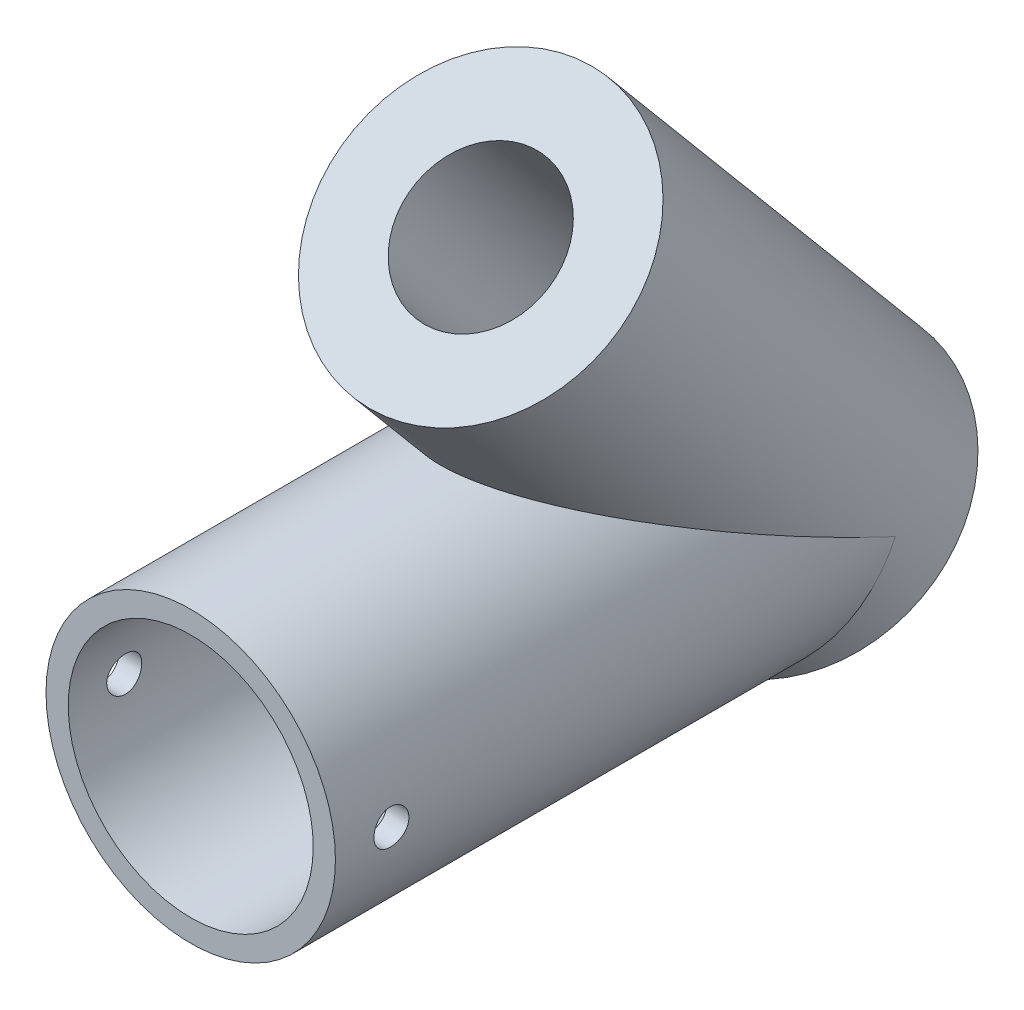
SolidWorks part; units mm, degrees
ref_plane "Front Plane" through (0, 0, 0) normal (0, 0, 1) x (1, 0, 0)
ref_plane "Top Plane" through (0, 0, 0) normal (0, 1, 0) x (1, 0, 0)
ref_plane "Right Plane" through (0, 0, 0) normal (1, 0, 0) x (0, 0, -1)
sketch "Sketch1" plane through (0, 0, 0) normal (0, 0, 1) x (1, 0, 0)
  circle A0 centre (0, 0) radius 17.5
  circle A1 centre (0, 0) radius 20.675
  dimension "D1" = 35
  dimension "D2" = 41.35
extrude "Boss-Extrude1" add sketch "Sketch1" along normal blind 60
sketch "Sketch2" plane through (0, 0, 0) normal (1, 0, 0) x (0, 0, -1)
  line L0 (0, 0) -> (20, 0) construction
  line L1 (20, 0) -> (-18.5673, 45.9627)
  dimension "D1" = 20
  dimension "D2" = 50
  dimension "D3" = 60
ref_plane "Plane4" through (0, 45.9627, 18.5673) normal (0, 0.766, 0.6428) x (1, 0, 0)
sketch "Sketch3" plane through (0, 45.9627, 18.5673) normal (0, 0.766, 0.6428) x (1, 0, 0)
  line L0 (0, -15.3209) -> (0, 0) construction
  line L1 (0, 10.5) -> (0, 20.675) construction
  line L2 (0, 10.5) -> (0, 0) construction
  circle A0 centre (0, 0) radius 20.675
  circle A1 centre (0, 0) radius 10.5
  dimension "D2" = 41.35
  dimension "D1" = 21
extrude "Boss-Extrude2" add sketch "Sketch3" against normal blind 70
extrude "Boss-Extrude5" add sketch "Sketch1<4>" against normal up to surface (5.6283 mm away) up to face at (0, 32.673, 34.4052)
sketch "Sketch1<4>" plane through (0, 0, 0) normal (0, 0, 1) x (1, 0, 0) same geometry as "Sketch1"
sketch "Sketch6" plane through (0, 36.1146, 30.3037) normal (0, 0.766, 0.6428) x (1, 0, 0)
  circle A0 centre (0, 15.3209) radius 10.5
  dimension "D1" = 21
extrude "Cut-Extrude1" cut sketch "Sketch6" against normal through all both
sketch "Sketch7" plane through (0, 0, 0) normal (1, 0, 0) x (0, 0, -1)
  line L0 (-60, 0) -> (-52, 0) construction
  line L1 (-60, 20.675) -> (-60, -20.675) construction
  circle A0 centre (-52, 0) radius 2.5
  dimension "D2" = 5
  dimension "D1" = 8
extrude "Cut-Extrude2" cut sketch "Sketch7" against normal through all both and the other way through all
equation "\"tubeOutDiameter\" = 35mm"
equation "\"wheelShaftDiameter\"= 12mm"
equation "\"wheelThickness\"= 135mm"
equation "\"BearingDiameter\"= 20mm"
equation "\"BearingThickness\"= 10mm"
equation "\"frontShaftDiameter\"= 20mm"
equation "\"D2@Sketch1\"=\"tubeOutDiameter\"+0.25in"
equation "\"D1@Sketch3\"=21mm"
equation "\"D2@Sketch3\"=\"tubeOutDiameter\"+0.25in"
